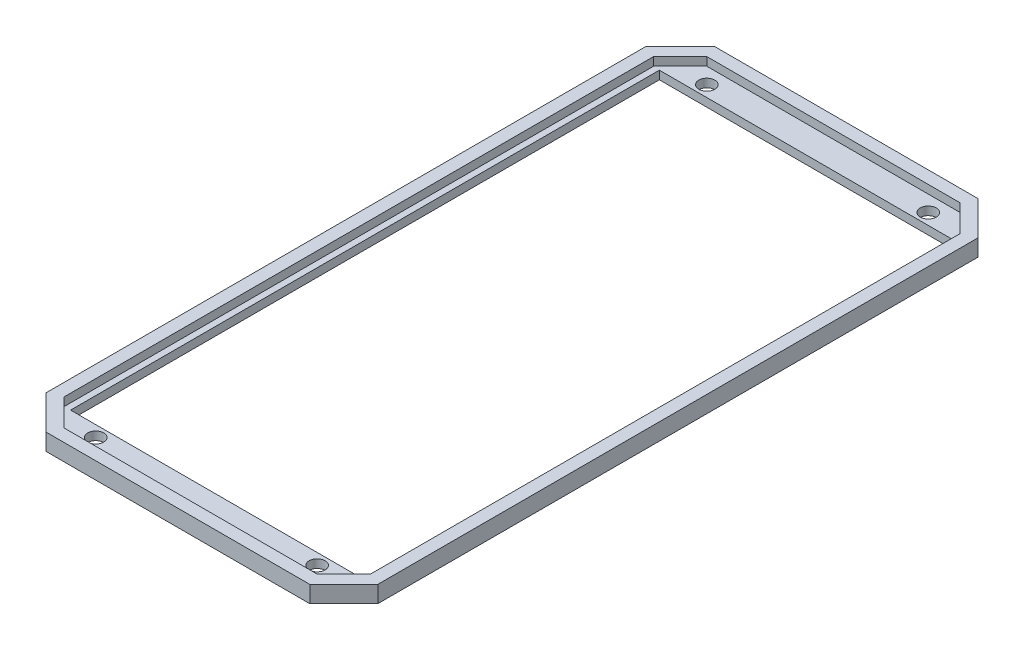
SolidWorks part; units mm, degrees
ref_plane "Front Plane" through (0, 0, 0) normal (0, 0, 1) x (1, 0, 0)
ref_plane "Top Plane" through (0, 0, 0) normal (0, 1, 0) x (1, 0, 0)
ref_plane "Right Plane" through (0, 0, 0) normal (1, 0, 0) x (0, 0, -1)
sketch "Sketch1" plane through (0, 0, 0) normal (0, 1, 0) x (1, 0, 0)
  line L0 (-19.1494, -87.1542) -> (-19.1494, 56.0471)
  line L1 (-22.1494, -85.9116) -> (-22.1494, 54.8044)
  line L2 (-28.4994, -92.2615) -> (-22.1494, -85.9116)
  line L3 (-88.9514, -92.2615) -> (-28.4994, -92.2615)
  line L4 (-90.1941, -95.2615) -> (-27.2568, -95.2615)
  line L5 (-27.2568, -95.2615) -> (-19.1494, -87.1542)
  line L6 (-93.8014, -85.7902) -> (-23.6494, -85.7902)
  line L7 (-95.3014, -85.9115) -> (-88.9514, -92.2615)
  line L8 (-98.3014, -87.1542) -> (-90.1941, -95.2615)
  line L9 (-93.8014, 54.6832) -> (-23.6494, 54.6832)
  line L10 (-95.3014, 54.8045) -> (-95.3014, -85.9115)
  line L11 (-98.3014, 56.0471) -> (-98.3014, -87.1542)
  line L12 (-23.6494, -85.7902) -> (-23.6494, 54.1832) construction
  line L14 (-22.1494, 54.8044) -> (-28.4996, 61.1545)
  line L15 (-19.1494, 56.0471) -> (-27.2568, 64.1616)
  line L16 (-27.2568, 64.1616) -> (-90.1941, 64.1616)
  line L17 (-28.4996, 61.1545) -> (-88.9514, 61.1545)
  line L18 (-88.9514, 61.1545) -> (-95.3014, 54.8045)
  line L19 (-90.1941, 64.1616) -> (-98.3014, 56.0471)
  line L20 (-93.8014, 54.1832) -> (-93.8014, -85.7902) construction
  line L21 (-94.3014, 54.6832) -> (-23.1494, 54.6832) construction
  line L27 (-93.8014, 54.6832) -> (-93.8014, -85.7902)
  line L31 (-23.6494, -85.7902) -> (-23.6494, 54.6832)
  line L53 (-94.3014, 54.6832) -> (-94.3014, -86.2902) construction
  line L54 (-23.1494, -86.2902) -> (-23.1494, 54.6832) construction
  line L55 (-93.8014, 54.1832) -> (-23.6494, 54.1832) construction
  line L56 (-94.3014, -86.2902) -> (-23.1494, -86.2902) construction
  circle A0 centre (-85.1414, -88.4515) radius 1.905
  circle A1 centre (-32.3094, -88.4515) radius 1.905
  circle A2 centre (-32.3094, 57.3445) radius 1.905
  circle A3 centre (-85.1414, 57.3445) radius 1.905
  point P0 (-27.2568, -95.2615)
extrude "Boss-Extrude1" add sketch "Sketch1" along normal blind 2 contours L16 L19 L11 L8 L4 L5 L0 L15 L18 L17 L14 L1 L2 L3 L7 L10 | L17 L18 L10 L7 L3 L2 L1 L14 A2 A0 A1 A3 region at (-24.4617, 0, 89.9493) region at (-26.5262, 0, 87.8847)
extrude "Boss-Extrude2" add sketch "Sketch1<3>" along normal blind 4 contours L16 L19 L11 L8 L4 L5 L0 L15 L18 L17 L14 L1 L2 L3 L7 L10 region at (-24.4617, 0, 89.9493)
sketch "Sketch1<3>" plane through (0, 0, 0) normal (0, 1, 0) x (1, 0, 0) same geometry as "Sketch1"
